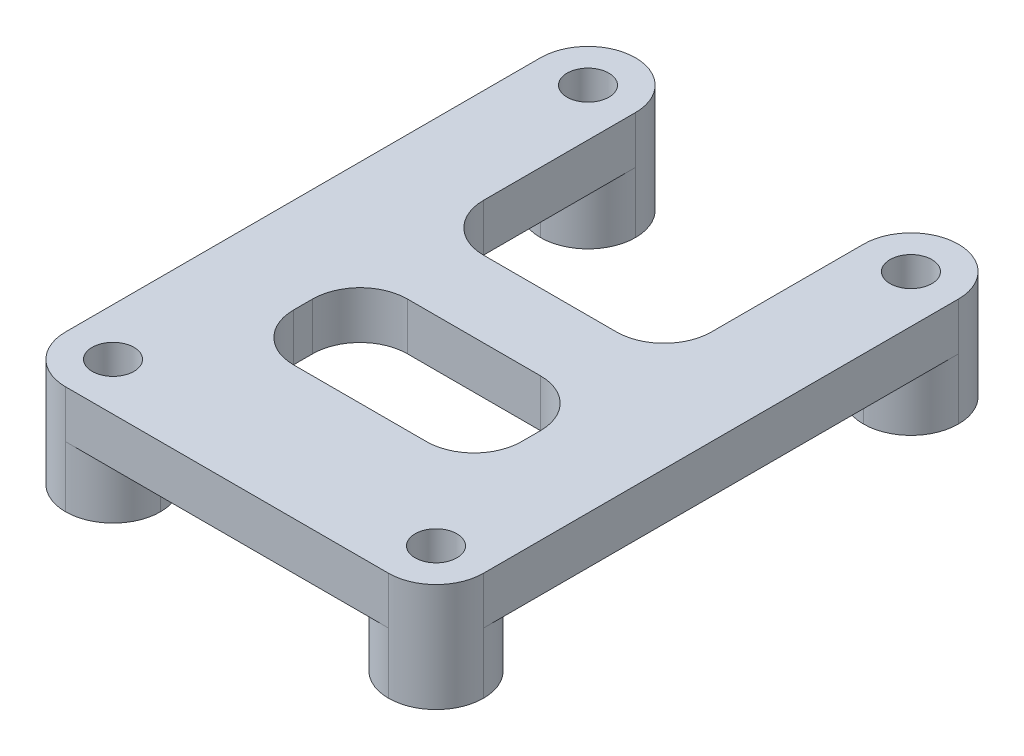
SolidWorks part; units mm, degrees
ref_plane "Front Plane" through (0, 0, 0) normal (0, 0, 1) x (1, 0, 0)
ref_plane "Top Plane" through (0, 0, 0) normal (0, 1, 0) x (1, 0, 0)
ref_plane "Right Plane" through (0, 0, 0) normal (1, 0, 0) x (0, 0, -1)
sketch "Sketch1" plane through (0, 0, 0) normal (0, 1, 0) x (1, 0, 0)
  line L1 (-20, 10) -> (20, 10) construction
  line L2 (-20, 10) -> (-20, -10) construction
  line L3 (-20, -10) -> (20, -10) construction
  line L4 (20, 10) -> (20, -10) construction
  line L5 (-6, 2) -> (6, 2)
  line L6 (-6, 2) -> (-6, -10)
  line L7 (-6, -10) -> (6, -10)
  line L8 (6, 2) -> (6, -10)
  line L9 (6, 10) -> (11, 10)
  line L10 (6, 10) -> (6, -10)
  line L11 (6, -10) -> (11, -10)
  line L12 (11, 10) -> (11, -10)
  line L13 (-6, 10) -> (-11, 10)
  line L14 (-6, 10) -> (-6, -10)
  line L15 (-6, -10) -> (-11, -10)
  line L16 (-11, 10) -> (-11, -10)
  line L17 (-11, 10) -> (-6, 10)
  line L18 (-11, 10) -> (-11, 15)
  line L19 (-11, 15) -> (-6, 15)
  line L20 (-6, 10) -> (-6, 15)
  line L21 (6, 10) -> (11, 10)
  line L22 (6, 10) -> (6, 15)
  line L23 (6, 15) -> (11, 15)
  line L24 (11, 10) -> (11, 15)
  line L25 (-11, -10) -> (11, -10)
  line L26 (-11, -10) -> (-11, -15)
  line L27 (-11, -15) -> (11, -15)
  line L28 (11, -10) -> (11, -15)
  point P4 (0, 10)
  point P6 (-20, 0)
  point P17 (0, 2)
  dimension "D1" = 40
  dimension "D2" = 20
  dimension "D3" = 12
  dimension "D4" = 5
  dimension "D5" = 12
  dimension "D6" = 5
extrude "Boss-Extrude1" add sketch "Sketch1" along normal blind 2.5 contours L13 L16 L15 L6 L14 | L8 L5 L6 L7 | L12 L9 L10 L8 L11 | L9 L24 L23 L22 | L13 L20 L19 L18 | L28 L11 L7 L15 L26 L27 region at (0, 0, 4) region at (-8.5, 0, 0) region at (8.5, 0, 0) region at (0, 0, 12.5) region at (-8.5, 0, -12.5) region at (8.5, 0, -12.5)
sketch "Sketch2" plane through (0, 0, 0) normal (0, -1, 0) x (1, 0, 0)
  line L0 (-6, -15) -> (-6, -2) construction
  line L1 (-11, -15) -> (-6, -15)
  line L2 (-11, -15) -> (-11, -10)
  line L3 (-11, -10) -> (-6, -10)
  line L4 (-6, -15) -> (-6, -10)
  line L10 (0, 15) -> (0, -2) construction
  line L11 (-11, 15) -> (11, 15) construction
  line L12 (-6, -2) -> (6, -2) construction
  line L13 (-11, -15) -> (-11, 15) construction
  line L14 (-11, 0) -> (11, 0) construction
  line L15 (11, -15) -> (11, 15) construction
  line L16 (-11, 10) -> (-6, 10)
  line L17 (-6, 15) -> (-6, 10)
  line L18 (-11, 15) -> (-6, 15)
  line L19 (-11, 15) -> (-11, 10)
  line L20 (11, -10) -> (6, -10)
  line L21 (6, -15) -> (6, -10)
  line L22 (11, -15) -> (6, -15)
  line L23 (11, -15) -> (11, -10)
  line L24 (11, 15) -> (11, 10)
  line L25 (11, 15) -> (6, 15)
  line L26 (6, 15) -> (6, 10)
  line L27 (11, 10) -> (6, 10)
  dimension "D1" = 5
extrude "Boss-Extrude2" add sketch "Sketch2" along normal blind 3.2
sketch "Sketch3" plane through (0, 2.5, 0) normal (0, 1, 0) x (1, 0, 0)
  line L0 (-11, 15) -> (-6, 15) construction
  line L1 (0, 2) -> (0, -15) construction
  line L2 (-6, 2) -> (6, 2) construction
  line L3 (-11, -15) -> (11, -15) construction
  line L4 (-11, 0) -> (11, 0) construction
  line L5 (-11, 15) -> (-11, -15) construction
  line L6 (11, 15) -> (11, -15) construction
  circle A0 centre (-8.5, 12.5) radius 1.1
  circle A1 centre (-8.5, -12.5) radius 1.1
  circle A2 centre (8.5, -12.5) radius 1.1
  circle A3 centre (8.5, 12.5) radius 1.1
  point P6 (-8.5, 15)
  dimension "D1" = 2.2
  dimension "D2" = 2.5
extrude "Cut-Extrude1" cut sketch "Sketch3" against normal through all
fillet "Fillet1" radius 2.5 18 edges at (-11, -1.6, -10) (6, -1.6, -10) (6, -1.6, 10) (11, -1.6, -10) (-6, -1.6, -10) (-11, -1.6, 10) (-6, -1.6, 10) (11, -1.6, 10) (11, -0.35, 15) (-6, -1.6, 15) (6, -1.6, 15) (-11, -0.35, 15) (-11, -0.35, -15) (-6, -0.35, -15) (11, -0.35, -15) (6, -0.35, -15) (6, 1.25, -2) (-6, 1.25, -2)
sketch "Sketch4" plane through (0, 2.5, 0) normal (0, 1, 0) x (1, 0, 0)
  line L0 (-3.5, 2) -> (3.5, 2) construction
  line L1 (-3.5, -2) -> (3.5, -2)
  line L2 (-6, -4.5) -> (-6, -5.5)
  line L3 (-3.5, -8) -> (3.5, -8)
  line L4 (6, -4.5) -> (6, -5.5)
  arc A0 (3.5, -2) -> (6, -4.5) centre (3.5, -4.5) cw
  arc A1 (3.5, -8) -> (6, -5.5) centre (3.5, -5.5) ccw
  arc A2 (-6, -5.5) -> (-3.5, -8) centre (-3.5, -5.5) ccw
  arc A3 (-3.5, -2) -> (-6, -4.5) centre (-3.5, -4.5) ccw
  point P4 (0, -2)
  point P10 (6, -2)
  point P15 (-6, -8)
  point P18 (-6, -2)
  dimension "D4" = 2.5
  dimension "D1" = 12
  dimension "D2" = 6
  dimension "D3" = 4
extrude "Cut-Extrude2" cut sketch "Sketch4" against normal through all
